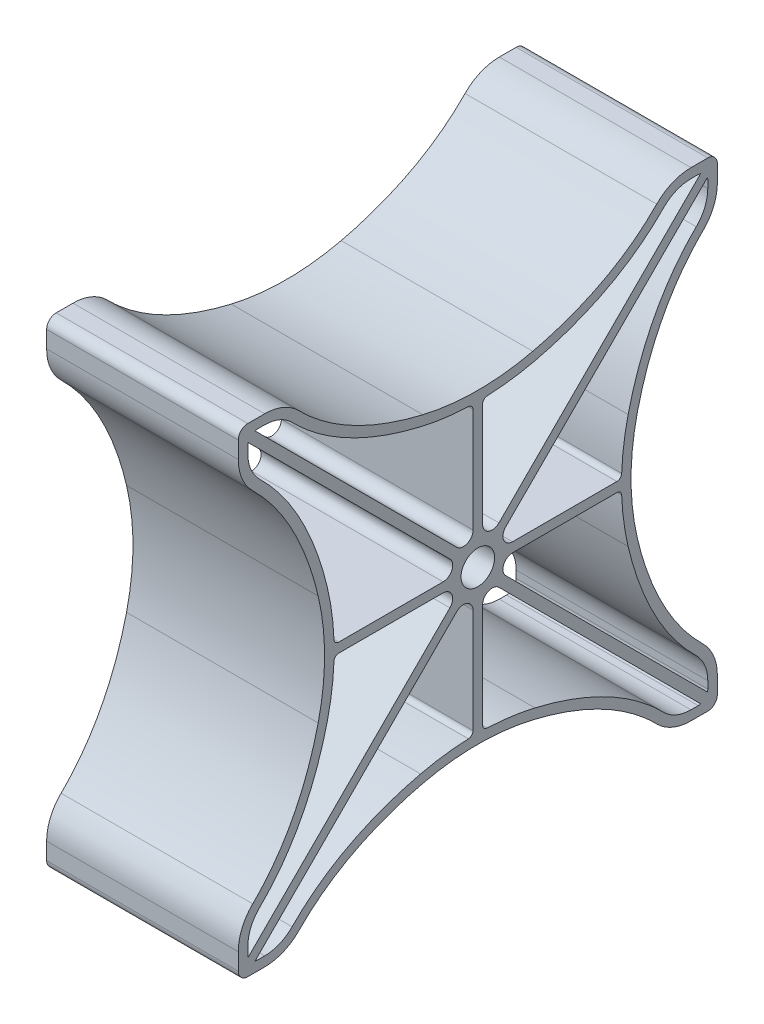
SolidWorks part; units mm, degrees
ref_plane "Front Plane" through (0, 0, 0) normal (0, 0, 1) x (1, 0, 0)
ref_plane "Top Plane" through (0, 0, 0) normal (0, 1, 0) x (1, 0, 0)
ref_plane "Right Plane" through (0, 0, 0) normal (1, 0, 0) x (0, 0, -1)
sketch "Sketch1" plane through (0, 0, 0) normal (1, 0, 0) x (0, 0, -1)
  line L0 (100, 0) -> (100, -5.5098)
  line L1 (0, 0) -> (100, 0) construction
  line L2 (0, 0) -> (0, -100) construction
  line L3 (0, -100) -> (100, -100) construction
  line L5 (2, -2) -> (2, -5.5098)
  line L6 (2, -98) -> (2, -94.4902)
  line L7 (100, -100) -> (100, -94.4902)
  line L8 (2, -98) -> (5.5098, -98)
  line L10 (0, 0) -> (5.5098, 0)
  line L11 (100, 0) -> (94.4902, 0)
  line L12 (100, -100) -> (94.4902, -100)
  line L13 (0, -100) -> (5.5098, -100)
  line L14 (0, -100) -> (0, -94.4902)
  line L15 (0, 0) -> (0, -5.5098)
  line L16 (98, -98) -> (94.4902, -98)
  line L17 (98, -98) -> (98, -94.4902)
  line L18 (98, -2) -> (98, -5.5098)
  line L19 (98, -2) -> (94.4902, -2)
  line L20 (2, -2) -> (5.5098, -2)
  arc A0 (96.9874, -12.6635) -> (100, -5.5098) centre (90, -5.5098) ccw
  arc A1 (96.9874, -87.3365) -> (100, -94.4902) centre (90, -94.4902) cw
  arc A2 (83.3208, -61.4746) -> (83.3208, -38.5254) centre (131.9863, -50) cw
  arc A3 (38.5254, -16.6792) -> (61.4746, -16.6792) centre (50, 31.9863) ccw
  arc A4 (12.6635, -3.0126) -> (5.5098, 0) centre (5.5098, -10) ccw
  arc A5 (87.3365, -3.0126) -> (94.4902, 0) centre (94.4902, -10) cw
  arc A6 (87.3365, -96.9874) -> (94.4902, -100) centre (94.4902, -90) ccw
  arc A7 (61.4746, -83.3208) -> (38.5254, -83.3208) centre (50, -131.9863) ccw
  arc A8 (12.6635, -96.9874) -> (5.5098, -100) centre (5.5098, -90) cw
  arc A9 (3.0126, -87.3365) -> (0, -94.4902) centre (10, -94.4902) ccw
  arc A10 (16.6792, -38.5254) -> (16.6792, -61.4746) centre (-31.9863, -50) cw
  arc A11 (3.0126, -12.6635) -> (0, -5.5098) centre (10, -5.5098) cw
  arc A12 (4.41, -11.2328) -> (2, -5.5098) centre (10, -5.5098) cw
  arc A13 (18.6258, -38.0664) -> (18.6258, -61.9336) centre (-31.9863, -50) cw
  arc A14 (4.41, -88.7672) -> (2, -94.4902) centre (10, -94.4902) ccw
  arc A15 (11.2328, -95.59) -> (5.5098, -98) centre (5.5098, -90) cw
  arc A16 (61.9336, -81.3742) -> (38.0664, -81.3742) centre (50, -131.9863) ccw
  arc A17 (88.7672, -95.59) -> (94.4902, -98) centre (94.4902, -90) ccw
  arc A18 (95.59, -88.7672) -> (98, -94.4902) centre (90, -94.4902) cw
  arc A19 (81.3742, -61.9336) -> (81.3742, -38.0664) centre (131.9863, -50) cw
  arc A20 (95.59, -11.2328) -> (98, -5.5098) centre (90, -5.5098) ccw
  arc A21 (88.7672, -4.41) -> (94.4902, -2) centre (94.4902, -10) cw
  arc A22 (38.0664, -18.6258) -> (61.9336, -18.6258) centre (50, 31.9863) ccw
  arc A23 (11.2328, -4.41) -> (5.5098, -2) centre (5.5098, -10) ccw
  spline S0 degree 3 poles (96.9874, -12.6635) (94.285, -15.3032) (88.726, -22.5012) (85.0016, -31.8334) (83.5063, -37.7385) (83.3208, -38.5254) knots 0.087568 0.087568 0.087568 0.087568 0.33605 0.688962 0.74236 0.74236 0.74236 0.74236
  spline S1 degree 3 poles (96.9874, -87.3365) (94.285, -84.6968) (88.726, -77.4988) (85.0016, -68.1666) (83.5063, -62.2615) (83.3208, -61.4746) knots 0.087568 0.087568 0.087568 0.087568 0.33605 0.688962 0.74236 0.74236 0.74236 0.74236
  spline S2 degree 3 poles (12.6635, -3.0126) (15.3032, -5.715) (22.5012, -11.274) (31.8334, -14.9984) (37.7385, -16.4937) (38.5254, -16.6792) knots 0.087568 0.087568 0.087568 0.087568 0.33605 0.688962 0.74236 0.74236 0.74236 0.74236
  spline S3 degree 3 poles (87.3365, -3.0126) (84.6968, -5.715) (77.4988, -11.274) (68.1666, -14.9984) (62.2615, -16.4937) (61.4746, -16.6792) knots 0.087568 0.087568 0.087568 0.087568 0.33605 0.688962 0.74236 0.74236 0.74236 0.74236
  spline S4 degree 3 poles (87.3365, -96.9874) (84.6968, -94.285) (77.4988, -88.726) (68.1666, -85.0016) (62.2615, -83.5063) (61.4746, -83.3208) knots 0.087568 0.087568 0.087568 0.087568 0.33605 0.688962 0.74236 0.74236 0.74236 0.74236
  spline S5 degree 3 poles (12.6635, -96.9874) (15.3032, -94.285) (22.5012, -88.726) (31.8334, -85.0016) (37.7385, -83.5063) (38.5254, -83.3208) knots 0.087568 0.087568 0.087568 0.087568 0.33605 0.688962 0.74236 0.74236 0.74236 0.74236
  spline S6 degree 3 poles (3.0126, -87.3365) (5.715, -84.6968) (11.274, -77.4988) (14.9984, -68.1666) (16.4937, -62.2615) (16.6792, -61.4746) knots 0.087568 0.087568 0.087568 0.087568 0.33605 0.688962 0.74236 0.74236 0.74236 0.74236
  spline S7 degree 3 poles (3.0126, -12.6635) (5.715, -15.3032) (11.274, -22.5012) (14.9984, -31.8334) (16.4937, -37.7385) (16.6792, -38.5254) knots 0.087568 0.087568 0.087568 0.087568 0.33605 0.688962 0.74236 0.74236 0.74236 0.74236
  spline S8 degree 1 poles (4.41, -11.2328) (18.6258, -38.0664) knots 0 0 1 1 construction
  spline S9 degree 1 poles (4.41, -88.7672) (18.6258, -61.9336) knots 0 0 1 1 construction
  spline S10 degree 1 poles (11.2328, -95.59) (38.0664, -81.3742) knots 0 0 1 1 construction
  spline S11 degree 1 poles (88.7672, -95.59) (61.9336, -81.3742) knots 0 0 1 1 construction
  spline S12 degree 1 poles (95.59, -88.7672) (81.3742, -61.9336) knots 0 0 1 1 construction
  spline S13 degree 1 poles (95.59, -11.2328) (81.3742, -38.0664) knots 0 0 1 1 construction
  spline S14 degree 1 poles (88.7672, -4.41) (61.9336, -18.6258) knots 0 0 1 1 construction
  spline S15 degree 1 poles (11.2328, -4.41) (38.0664, -18.6258) knots 0 0 1 1 construction
  spline S16 degree 3 poles (4.41, -11.2328) (5.3388, -12.14) (7.1194, -14.0455) (10.2989, -18.1041) (13.6193, -23.6203) (16.6303, -30.724) (18.0432, -35.5953) (18.6258, -38.0664) knots 0.087568 0.087568 0.087568 0.087568 0.169417 0.251266 0.414964 0.578662 0.74236 0.74236 0.74236 0.74236
  spline S17 degree 3 poles (18.6258, -61.9336) (18.0432, -64.4047) (16.6303, -69.276) (13.6193, -76.3797) (10.2989, -81.8959) (7.1194, -85.9545) (5.3388, -87.86) (4.41, -88.7672) knots 0.087568 0.087568 0.087568 0.087568 0.251266 0.414964 0.578662 0.660511 0.74236 0.74236 0.74236 0.74236
  spline S18 degree 3 poles (11.2328, -95.59) (12.14, -94.6612) (14.0455, -92.8806) (18.1041, -89.7011) (23.6203, -86.3807) (30.724, -83.3697) (35.5953, -81.9568) (38.0664, -81.3742) knots 0.087568 0.087568 0.087568 0.087568 0.169417 0.251266 0.414964 0.578662 0.74236 0.74236 0.74236 0.74236
  spline S19 degree 3 poles (61.9336, -81.3742) (64.4047, -81.9568) (69.276, -83.3697) (76.3797, -86.3807) (81.8959, -89.7011) (85.9545, -92.8806) (87.86, -94.6612) (88.7672, -95.59) knots 0.087568 0.087568 0.087568 0.087568 0.251266 0.414964 0.578662 0.660511 0.74236 0.74236 0.74236 0.74236
  spline S20 degree 3 poles (95.59, -88.7672) (94.6612, -87.86) (92.8806, -85.9545) (89.7011, -81.8959) (86.3807, -76.3797) (83.3697, -69.276) (81.9568, -64.4047) (81.3742, -61.9336) knots 0.087568 0.087568 0.087568 0.087568 0.169417 0.251266 0.414964 0.578662 0.74236 0.74236 0.74236 0.74236
  spline S21 degree 3 poles (81.3742, -38.0664) (81.9568, -35.5953) (83.3697, -30.724) (86.3807, -23.6203) (89.7011, -18.1041) (92.8806, -14.0455) (94.6612, -12.14) (95.59, -11.2328) knots 0.087568 0.087568 0.087568 0.087568 0.251266 0.414964 0.578662 0.660511 0.74236 0.74236 0.74236 0.74236
  spline S22 degree 3 poles (88.7672, -4.41) (87.86, -5.3388) (85.9545, -7.1194) (81.8959, -10.2989) (76.3797, -13.6193) (69.276, -16.6303) (64.4047, -18.0432) (61.9336, -18.6258) knots 0.087568 0.087568 0.087568 0.087568 0.169417 0.251266 0.414964 0.578662 0.74236 0.74236 0.74236 0.74236
  spline S23 degree 3 poles (38.0664, -18.6258) (35.5953, -18.0432) (30.724, -16.6303) (23.6203, -13.6193) (18.1041, -10.2989) (14.0455, -7.1194) (12.14, -5.3388) (11.2328, -4.41) knots 0.087568 0.087568 0.087568 0.087568 0.251266 0.414964 0.578662 0.660511 0.74236 0.74236 0.74236 0.74236
  dimension "D1" = 10
  dimension "D2" = 50
  dimension "D3" = 2
extrude "Boss-Extrude1" add sketch "Sketch1" along normal blind 40
fillet "Fillet1" radius 2 8 edges at (20, 0, 0) (20, -2, -2) (20, -100, 0) (20, -98, -2) (20, 0, -100) (20, -2, -98) (20, -100, -100) (20, -98, -98)
sketch "Sketch2" plane through (0, 0, 0) normal (-1, 0, 0) x (0, 0, 1)
  line L0 (-50, -20.0137) -> (-50, -79.9863) construction
  line L1 (-20.0137, -50) -> (-79.9863, -50) construction
ref_plane "Plane1" through (0, 0, -50) normal (0, 0, -1) x (0, -1, 0)
ref_plane "Plane2" through (0, -50, 0) normal (0, 1, 0) x (0, 0, -1)
ref_axis "Axis1" through (55, -50, -50) along (-1, 0, 0)
sketch "Sketch3" plane through (0, 0, 0) normal (-1, 0, 0) x (0, 0, 1)
  line L0 (-97.4489, -98.8632) -> (-54.4142, -55.8284)
  line L1 (-99.1183, -2.2959) -> (-55.8284, -45.5858)
  line L2 (-97.5632, -1.0226) -> (-99.1183, -2.2959)
  line L3 (-18.9935, -49) -> (-42.7574, -49)
  line L4 (-51, -18.426) -> (-51, -42.7574)
  line L5 (-49, -18.426) -> (-49, -42.7574)
  line L6 (-97.5632, -1.0226) -> (-54.4142, -44.1716)
  line L7 (-98.8632, -97.4489) -> (-55.8284, -54.4142)
  line L8 (-18.9935, -51) -> (-42.7574, -51)
  line L9 (-2.4368, -1.0226) -> (-1.0226, -2.4368)
  line L10 (-51, -18.426) -> (-49, -18.426)
  line L11 (-18.9935, -49) -> (-18.9935, -51)
  line L12 (-1.0226, -97.5632) -> (-2.4368, -98.9774)
  line L13 (-51, -80.7947) -> (-49, -80.7947)
  line L14 (-98.8632, -97.4489) -> (-97.4489, -98.8632)
  line L15 (-80.9422, -49) -> (-80.9422, -51)
  line L16 (-50, 199979.9863) -> (-50, -200079.9863) construction
  line L18 (-57.2426, -49) -> (-80.9422, -49)
  line L21 (-57.2426, -51) -> (-80.9422, -51)
  line L22 (-51, -57.2426) -> (-51, -80.7947)
  line L24 (-45.5858, -55.8284) -> (-2.4368, -98.9774)
  line L25 (-49, -57.2426) -> (-49, -80.7947)
  line L27 (-44.1716, -54.4142) -> (-1.0226, -97.5632)
  line L28 (-44.1716, -45.5858) -> (-1.0226, -2.4368)
  line L31 (-45.5858, -44.1716) -> (-2.4368, -1.0226)
  arc A8 (-54.4142, -44.1716) -> (-51, -42.7574) centre (-53, -42.7574) ccw
  arc A9 (-45.5858, -44.1716) -> (-49, -42.7574) centre (-47, -42.7574) cw
  arc A10 (-42.7574, -49) -> (-44.1716, -45.5858) centre (-42.7574, -47) cw
  arc A11 (-44.1716, -54.4142) -> (-42.7574, -51) centre (-42.7574, -53) cw
  arc A12 (-49, -57.2426) -> (-45.5858, -55.8284) centre (-47, -57.2426) cw
  arc A13 (-51, -57.2426) -> (-54.4142, -55.8284) centre (-53, -57.2426) ccw
  arc A14 (-55.8284, -54.4142) -> (-57.2426, -51) centre (-57.2426, -53) ccw
  arc A15 (-57.2426, -49) -> (-55.8284, -45.5858) centre (-57.2426, -47) ccw
  circle A16 centre (-50, -50) radius 3.5
  point P38 (-49, -52.4142)
  point P43 (-52.4142, -51)
  dimension "D1" = 2
  dimension "D2" = 2
  dimension "D3" = 2
  dimension "D4" = 2
  dimension "D5" = 2
  dimension "D6" = 2
  dimension "D7" = 2
  dimension "D8" = 2
extrude "Boss-Extrude2" add sketch "Sketch3" against normal blind 40
fillet "Fillet2" radius 1 8 edges at (20, -79.9959, -51) (20, -79.9959, -49) (20, -51, -79.9959) (20, -51, -20.0041) (20, -49, -20.0041) (20, -49, -79.9959) (20, -20.0041, -51) (20, -20.0041, -49)
